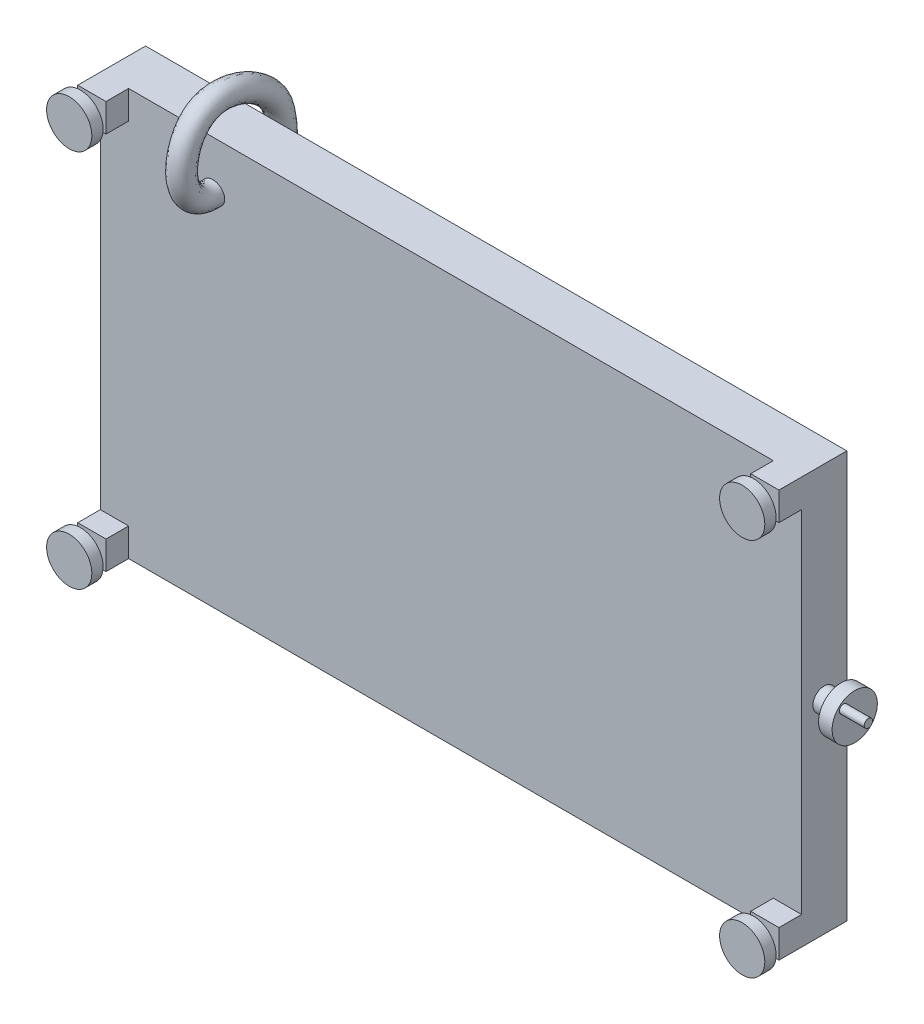
SolidWorks part; units mm, degrees
ref_plane "正面" through (0, 0, 0) normal (0, 0, 1) x (1, 0, 0)
ref_plane "平面" through (0, 0, 0) normal (0, 1, 0) x (1, 0, 0)
ref_plane "右側面" through (0, 0, 0) normal (1, 0, 0) x (0, 0, -1)
sketch "ｽｹｯﾁ1" plane through (0, 0, 0) normal (0, 0, 1) x (1, 0, 0)
  line L1 (0, 0) -> (620, 0)
  line L2 (0, 0) -> (0, 360)
  line L3 (0, 360) -> (620, 360)
  line L4 (620, 0) -> (620, 360)
  dimension "D1" = 360
  dimension "D2" = 620
extrude "ﾎﾞｽ - 押し出し2" add sketch "ｽｹｯﾁ1" along normal blind 40
sketch "ｽｹｯﾁ2" plane through (0, 0, 40) normal (0, 0, 1) x (1, 0, 0)
  line L1 (0, 360) -> (25, 360)
  line L2 (0, 360) -> (0, 335)
  line L3 (0, 335) -> (25, 335)
  line L4 (25, 360) -> (25, 335)
  line L5 (620, 360) -> (595, 360)
  line L6 (620, 360) -> (620, 335)
  line L7 (620, 335) -> (595, 335)
  line L8 (595, 360) -> (595, 335)
  line L9 (620, 0) -> (595, 0)
  line L10 (620, 0) -> (620, 25)
  line L11 (620, 25) -> (595, 25)
  line L12 (595, 0) -> (595, 25)
  line L13 (0, 0) -> (25, 0)
  line L14 (0, 0) -> (0, 25)
  line L15 (0, 25) -> (25, 25)
  line L16 (25, 0) -> (25, 25)
  dimension "D1" = 25
extrude "ﾎﾞｽ - 押し出し3" add sketch "ｽｹｯﾁ2" along normal blind 20
sketch "ｽｹｯﾁ3" plane through (0, 0, 60) normal (0, 0, 1) x (1, 0, 0)
  line L0 (0, 347.5) -> (620, 347.5) construction
  line L1 (0, 360) -> (0, 335) construction
  line L2 (620, 335) -> (620, 360) construction
  line L3 (0, 12.5) -> (620, 12.5) construction
  line L4 (0, 25) -> (0, 0) construction
  line L5 (620, 0) -> (620, 25) construction
  line L6 (12.5, 360) -> (12.5, 0) construction
  line L7 (25, 360) -> (0, 360) construction
  line L8 (0, 0) -> (25, 0) construction
  line L9 (607.5, 0) -> (607.5, 360) construction
  line L10 (595, 0) -> (620, 0) construction
  line L11 (620, 360) -> (595, 360) construction
  circle A0 centre (12.5, 347.5) radius 5
  circle A1 centre (607.5, 347.5) radius 5
  circle A2 centre (607.5, 12.5) radius 5
  circle A3 centre (12.5, 12.5) radius 5
  dimension "D1" = 10
extrude "ﾎﾞｽ - 押し出し4" add sketch "ｽｹｯﾁ3" along normal blind 10
sketch "ｽｹｯﾁ4" plane through (0, 0, 70) normal (0, 0, 1) x (1, 0, 0)
  circle A0 centre (12.5, 347.5) radius 20
  circle A1 centre (607.5, 347.5) radius 20
  circle A2 centre (607.5, 12.5) radius 20
  circle A3 centre (12.5, 12.5) radius 20
  dimension "D1" = 40
extrude "ﾎﾞｽ - 押し出し5" add sketch "ｽｹｯﾁ4" along normal blind 10
sketch "ｽｹｯﾁ8" plane through (620, 0, 0) normal (1, 0, 0) x (0, 0, -1)
  line L0 (-40, 180) -> (0, 180) construction
  line L1 (-40, 25) -> (-40, 335) construction
  line L2 (0, 0) -> (0, 360) construction
  line L3 (-20, 0) -> (-20, 360) construction
  line L4 (-60, 360) -> (0, 360) construction
  circle A0 centre (-20, 180) radius 10
  point P11 (-20, 180)
  dimension "D1" = 20
extrude "ﾎﾞｽ - 押し出し9" add sketch "ｽｹｯﾁ8" along normal blind 15
sketch "ｽｹｯﾁ9" plane through (635, 0, 0) normal (1, 0, 0) x (0, 0, -1)
  circle A0 centre (-20, 180) radius 20
  dimension "D1" = 40
extrude "ﾎﾞｽ - 押し出し10" add sketch "ｽｹｯﾁ9" along normal blind 12
sketch "ｽｹｯﾁ10" plane through (647, 0, 0) normal (1, 0, 0) x (0, 0, -1)
  circle A0 centre (-29.9045, 190.9287) radius 3.7102
extrude "ﾎﾞｽ - 押し出し11" add sketch "ｽｹｯﾁ10" along normal blind 22
ref_plane "平面1" through (100, 0, 0) normal (-1, 0, 0) x (0, 0, 1)
sketch "ｽｹｯﾁ11" plane through (100, 0, 0) normal (-1, 0, 0) x (0, 0, 1)
  spline S0 degree 3 poles (39.965, 317.9962) (76.4049, 315.6959) (72.8554, 415.046) (-21.9302, 374.2269) (-19.4396, 337.058) (-21.1695, 325.1986) knots 0 0 0 0 0.437936 0.808532 1 1 1 1
sweep "ｽｲｰﾌﾟ1" add path "ｽｹｯﾁ11" circular profile diameter 20 parameters "D3"=20
